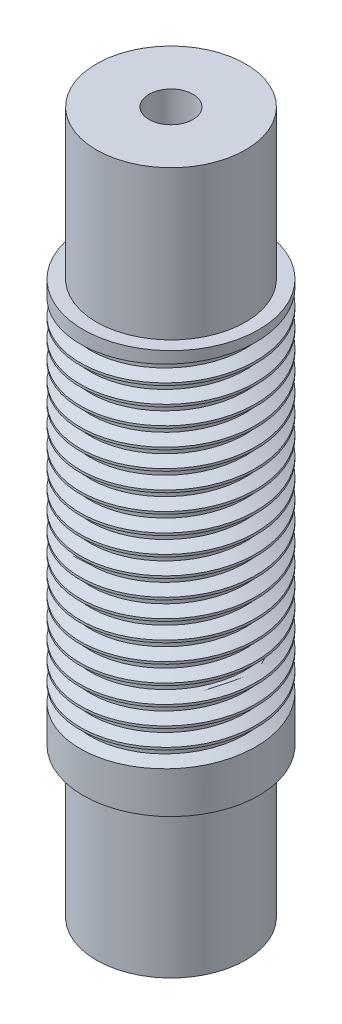
SolidWorks part; units mm, degrees
ref_plane "Front Plane" through (0, 0, 0) normal (0, 0, 1) x (1, 0, 0)
ref_plane "Top Plane" through (0, 0, 0) normal (0, 1, 0) x (1, 0, 0)
ref_plane "Right Plane" through (0, 0, 0) normal (1, 0, 0) x (0, 0, -1)
sketch "Sketch1" plane through (0, 0, 0) normal (0, 1, 0) x (1, 0, 0)
  circle A0 centre (0, 0) radius 10
  dimension "D1" = 20
extrude "Boss-Extrude1" add sketch "Sketch1" along normal mid plane 80
sketch "Sketch2" plane through (0, 40, 0) normal (0, 1, 0) x (1, 0, 0)
  circle A0 centre (0, 0) radius 8.5
  circle A1 centre (0, 0) radius 10
  dimension "D1" = 17
  dimension "D2" = 20
extrude "Cut-Extrude1" cut sketch "Sketch2" against normal blind 17
mirror "Mirror1" about plane through (0, 0, 0) normal (0, 1, 0) of "Cut-Extrude1"
thread "Thread1" pitch 2.1167 method cut profile "Thread Profile1" start angle 0, offset 0, length 40, pitch 2.1167, diameter 20
ref_plane "Plane1" through (-10, 23, 0) normal (0, 0, 1) x (-1, 0, 0)
sketch "Thread Profile1" plane through (-10, 23, 0) normal (0, 0, 1) x (-1, 0, 0)
  line L0 (0, 0) -> (0, 2.1167) construction
  line L11 (0, 0) -> (0, 1.8521)
  line L12 (0, 1.8521) -> (-1.1457, 1.1906)
  line L13 (-1.1457, 1.1906) -> (-1.1457, 0.6615)
  line L15 (-1.1457, 0.6615) -> (0, 0)
  line L17 (-1.1457, 0.926) -> (0, 0.926) construction
  point P2 (0, 0)
  dimension "Pitch" = 2.1167
  dimension "Profile_Angle" = 60
  dimension "Profile_Land" = 0.5292
  dimension "Profile_Height" = 1.1457
sketch "Sketch5" plane through (0, -40, 0) normal (0, -1, 0) x (1, 0, 0)
  circle A0 centre (0, 0) radius 2.5
  dimension "D1" = 5
extrude "Cut-Extrude2" cut sketch "Sketch5" against normal through all
